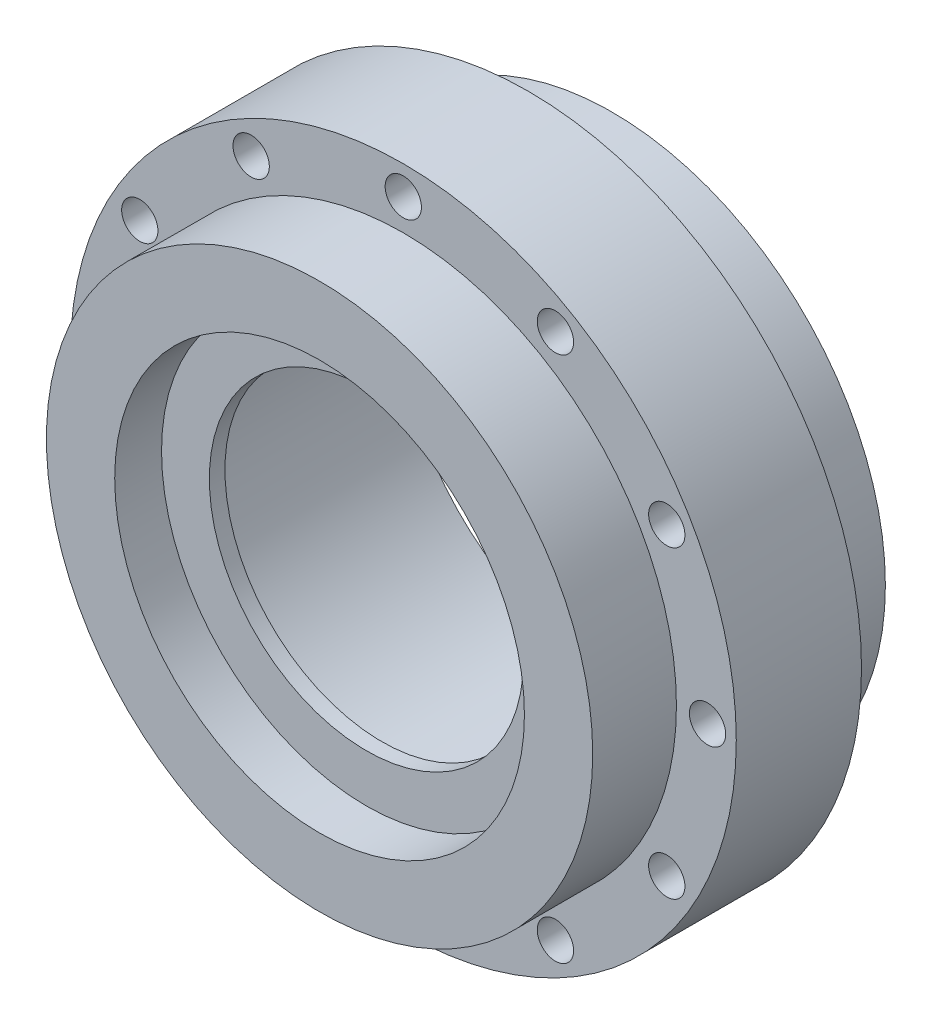
SolidWorks part; units mm, degrees
ref_plane "Front Plane" through (0, 0, 0) normal (0, 0, 1) x (1, 0, 0)
ref_plane "Top Plane" through (0, 0, 0) normal (0, 1, 0) x (1, 0, 0)
ref_plane "Right Plane" through (0, 0, 0) normal (1, 0, 0) x (0, 0, -1)
sketch "Sketch1" plane through (0, 0, 0) normal (1, 0, 0) x (0, 0, -1)
  line L0 (-84.7958, 52.5) -> (-72.7958, 52.5)
  line L1 (-73.3513, 52.5) -> (-74.0979, 52.5) construction
  line L3 (-50.0958, 55) -> (-67.2958, 55) construction
  line L4 (-84.7958, 52.5) -> (-84.7958, 70)
  line L5 (-84.7958, 70) -> (-9.7958, 70)
  line L6 (-72.7958, -51.9444) -> (-72.7958, 51.9445) construction
  line L7 (-72.7958, 52.5) -> (-72.7958, 40.25)
  line L8 (-72.7958, -48.3333) -> (-72.7958, 48.3333) construction
  line L9 (-72.7958, 40.25) -> (-68.7958, 40.25)
  line L10 (-68.7958, 53.5) -> (-68.7958, -53.5) construction
  line L11 (-68.7958, 40.25) -> (-68.7958, 55)
  line L12 (-68.7958, 55) -> (-9.7958, 55)
  line L14 (-9.7958, 70) -> (-9.7958, 55)
  line L15 (-68.7958, 40) -> (-82.7958, 40) construction
  line L16 (174.1864, 0) -> (-154.8488, 0) construction
  line L17 (-82.7958, 51.3889) -> (-82.7958, -51.3889) construction
  line L18 (-163.8227, 0) -> (139.4858, 0) construction
  dimension "D1" = 0.25
  dimension "D2" = 70
  dimension "D3" = 75
  dimension "D4" = 2
revolve "Revolve1" add sketch "Sketch1" angle 360 about L18
sketch "Sketch2" plane through (0, 0, 9.7958) normal (0, 0, -1) x (-1, 0, 0)
  line L0 (0, 62.5) -> (0, -62.5) construction
  circle A0 centre (0, 0) radius 62.5 construction
  circle A1 centre (0, 62.5) radius 4
  circle A2 centre (0, -62.5) radius 4
  dimension "D1" = 125
  dimension "D2" = 8
extrude "Cut-Extrude1" cut sketch "Sketch2" against normal blind 10
sketch "Sketch5" plane through (0, 0, 0) normal (0, 0, 1) x (1, 0, 0)
  line L0 (0, 70) -> (0, -70) construction
  line L3 (-31.25, 54.1266) -> (0, 0) construction
  line L8 (0, 62.5) -> (0, 0) construction
  line L9 (31.25, 54.1266) -> (0, 0) construction
  line L10 (54.1266, 31.25) -> (0, 0) construction
  line L11 (62.5, 0) -> (0, 0) construction
  line L12 (54.1266, -31.25) -> (0, 0) construction
  line L13 (31.25, -54.1266) -> (0, 0) construction
  line L14 (0, -62.5) -> (0, 0) construction
  line L15 (-31.25, -54.1266) -> (0, 0) construction
  line L16 (-54.1266, -31.25) -> (0, 0) construction
  line L17 (-62.5, 0) -> (0, 0) construction
  line L18 (-54.1266, 31.25) -> (0, 0) construction
  circle A0 centre (0, 0) radius 62.5 construction
  point P12 (-31.25, 54.1266)
  point P14 (-62.5, 0)
  point P15 (31.25, 54.1266)
  point P17 (62.5, 0)
  point P27 (54.1266, -31.25)
  point P28 (31.25, -54.1266)
  point P30 (-31.25, -54.1266)
  point P31 (-54.1266, -31.25)
  point P33 (-54.1266, 31.25)
  dimension "D1" = 125
  dimension "D3" = 12
  dimension "D2" = 30
hole_wizard "M8x1.25 Tapped Hole2" positions "Sketch5" profile "Sketch6" tap size "M8x1.25" standard "ANSI Metric"
sketch "Sketch6" plane through (-54.1266, 31.25, 0) normal (1, 0, 0) x (0, 1, 0)
  line L0 (0, 0) -> (0, 21.7929)
  line L1 (0, 21.7929) -> (3.4, 19.75)
  line L2 (3.4, 19.75) -> (3.4, 0)
  line L5 (3.4, 0) -> (0, 0)
  line L10 (0, 21.7929) -> (-3.4, 19.75) construction
  line L11 (0, -6.35) -> (0, 107.95) construction
  dimension "Tap Drill Dia." = 6.8
  dimension "Tap Drill Depth" = 19.75
  dimension "Drill Angle" = 118
cosmetic thread "Hole Thread8" parameters "D1"=16, "D2"=8
cosmetic thread "Hole Thread9" parameters "D1"=16, "D2"=8
cosmetic thread "Hole Thread10" parameters "D1"=16, "D2"=8
cosmetic thread "Hole Thread11" parameters "D1"=16, "D2"=8
cosmetic thread "Hole Thread12" parameters "D1"=16, "D2"=8
cosmetic thread "Hole Thread13" parameters "D1"=16, "D2"=8
cosmetic thread "Hole Thread14" parameters "D1"=16, "D2"=8
cosmetic thread "Hole Thread15" parameters "D1"=16, "D2"=8
cosmetic thread "Hole Thread16" parameters "D1"=16, "D2"=8
sketch "Sketch7" plane through (0, 0, 0) normal (1, 0, 0) x (0, 0, -1)
  line L0 (-31.2502, 70) -> (-63.3413, 70)
  line L1 (-84.7958, 70) -> (-9.7958, 70) construction
  line L2 (-63.3413, 70) -> (-63.3413, 85.3347)
  line L3 (-63.3413, 85.3347) -> (-31.2502, 85.3347)
  line L4 (-31.2502, 85.3347) -> (-31.2502, 70)
  point P5 (-47.2958, 70)
revolve "Revolve2" add sketch "Sketch7" angle 360 about L18
sketch "Sketch8" plane through (0, 0, 31.2502) normal (0, 0, -1) x (-1, 0, 0)
  circle A0 centre (0, 77.9691) radius 4.6522
  circle A1 centre (38.9846, 67.5233) radius 4.6522
  circle A2 centre (67.5233, 38.9846) radius 4.6522
  circle A3 centre (77.9691, 0) radius 4.6522
  circle A4 centre (67.5233, -38.9846) radius 4.6522
  circle A5 centre (38.9846, -67.5233) radius 4.6522
  circle A6 centre (0, -77.9691) radius 4.6522
  circle A7 centre (-38.9846, -67.5233) radius 4.6522
  circle A8 centre (-67.5233, -38.9846) radius 4.6522
  circle A9 centre (-77.9691, 0) radius 4.6522
  circle A10 centre (-67.5233, 38.9846) radius 4.6522
  circle A11 centre (-38.9846, 67.5233) radius 4.6522
  circle A12 centre (0, 0) radius 85.3347 construction
  point P29 (0, 0)
  dimension "D1" = 12
extrude "Cut-Extrude2" cut sketch "Sketch8" against normal through all
